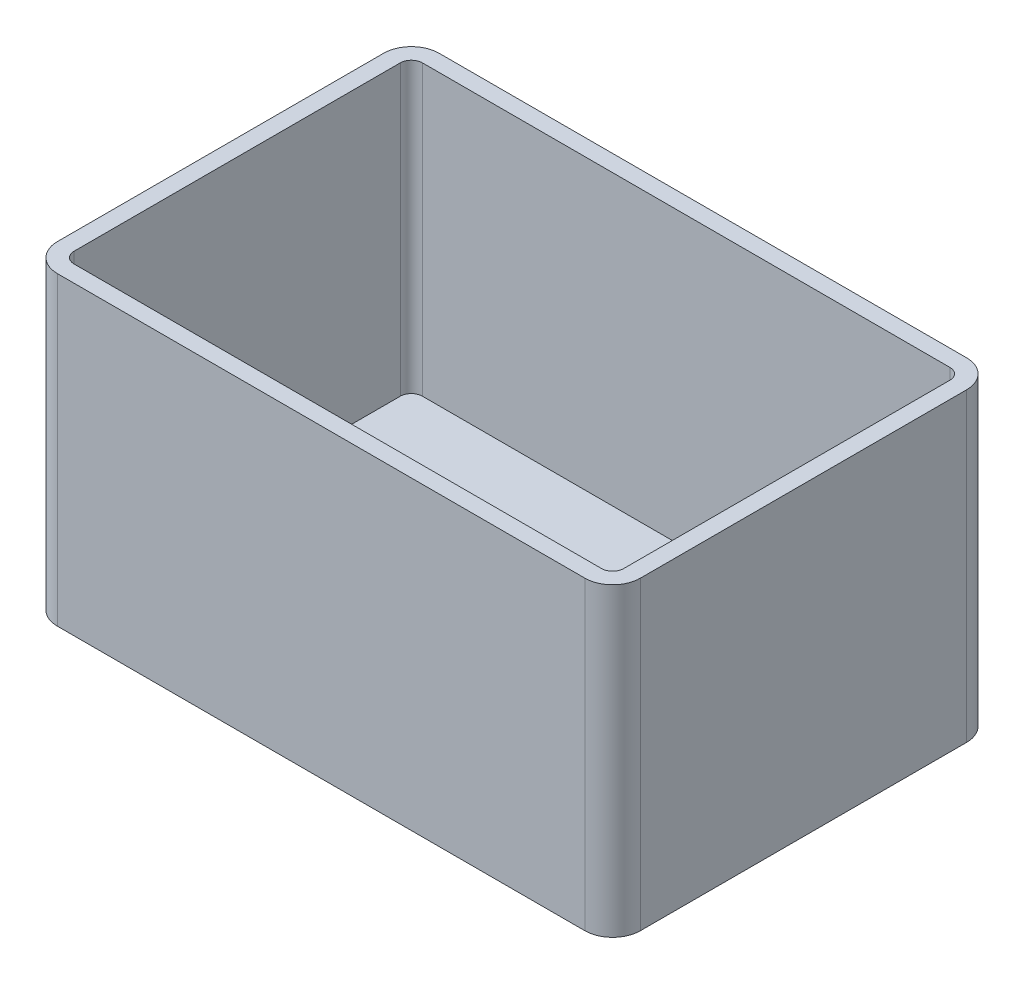
SolidWorks part; units mm, degrees
ref_plane "Front Plane" through (0, 0, 0) normal (0, 0, 1) x (1, 0, 0)
ref_plane "Top Plane" through (0, 0, 0) normal (0, 1, 0) x (1, 0, 0)
ref_plane "Right Plane" through (0, 0, 0) normal (1, 0, 0) x (0, 0, -1)
sketch "Sketch2" plane through (0, 0, 0) normal (0, 1, 0) x (1, 0, 0)
  line L1 (47.5, -34.375) -> (-47.5, -34.375)
  line L2 (52.5, -29.375) -> (52.5, 29.375)
  line L3 (47.5, 34.375) -> (-47.5, 34.375)
  line L4 (-52.5, -29.375) -> (-52.5, 29.375)
  arc A0 (-47.5, -34.375) -> (-52.5, -29.375) centre (-47.5, -29.375) cw
  arc A1 (47.5, -34.375) -> (52.5, -29.375) centre (47.5, -29.375) ccw
  arc A2 (52.5, 29.375) -> (47.5, 34.375) centre (47.5, 29.375) ccw
  arc A3 (-47.5, 34.375) -> (-52.5, 29.375) centre (-47.5, 29.375) ccw
  point P0 (0, 0)
  point P8 (-52.5, -34.375)
  point P13 (52.5, 34.375)
  point P16 (-52.5, 34.375)
  dimension "D3" = 5
  dimension "D1" = 105
  dimension "D2" = 68.75
extrude "Boss-Extrude1" add sketch "Sketch2" along normal blind 55
shell "Shell1" thickness 3 removed face at (0, 55, 0)
sketch "battery_connector_sketch" plane through (0, 3, 0) normal (0, 1, 0) x (1, 0, 0)
  line L0 (-43.2554, -24.8314) -> (-43.2554, -6.8814) construction
  line L1 (-48.2554, -4.8314) -> (-48.2554, -29.1314)
  line L2 (-46.2554, -31.1314) -> (-40.2554, -31.1314)
  line L3 (-40.2554, -2.8314) -> (-46.2554, -2.8314)
  line L4 (-39.5054, -13.4014) -> (-39.5054, -20.5614)
  line L5 (-38.2554, -4.8314) -> (-38.2554, -12.0614)
  line L6 (-38.2554, -29.1314) -> (-38.2554, -21.9014)
  line L7 (-38.2554, -12.0614) -> (-39.5054, -13.4014)
  line L8 (-38.2554, -21.9014) -> (-39.5054, -20.5614)
  line L9 (-41.26, -14.3503) -> (-45.2391, -14.3349)
  arc A0 (-38.2554, -4.8314) -> (-40.2554, -2.8314) centre (-40.2554, -4.8314) ccw
  arc A1 (-48.2554, -29.1314) -> (-46.2554, -31.1314) centre (-46.2554, -29.1314) ccw
  arc A2 (-40.2554, -31.1314) -> (-38.2554, -29.1314) centre (-40.2554, -29.1314) ccw
  arc A3 (-48.2554, -4.8314) -> (-46.2554, -2.8314) centre (-46.2554, -4.8314) cw
  circle A4 centre (-43.2554, -24.8314) radius 2.5
  circle A5 centre (-43.2554, -6.8814) radius 2.5
  arc A6 (-45.2391, -14.3349) -> (-41.26, -14.3503) centre (-43.2554, -15.8564) ccw
  circle A7 centre (-43.2554, -6.8814) radius 2.15
  circle A8 centre (-43.2554, -24.8314) radius 2.15
  dimension "D1" = 4.3
  dimension "D2" = 4.3
extrude "Cut-Extrude1" cut sketch "battery_connector_sketch" against normal blind 2 contours L1 A1 L2 A2 L6 L8 L4 L7 L5 A0 L3 A3
extrude "Cut-Extrude2" cut sketch "battery_connector_sketch<3>" against normal blind 3 contours A7
sketch "battery_connector_sketch<3>" plane through (0, 3, 0) normal (0, 1, 0) x (1, 0, 0) same geometry as "battery_connector_sketch"
extrude "Cut-Extrude3" cut sketch "battery_connector_sketch<4>" against normal blind 3 contours A8
sketch "battery_connector_sketch<4>" plane through (0, 3, 0) normal (0, 1, 0) x (1, 0, 0) same geometry as "battery_connector_sketch"
